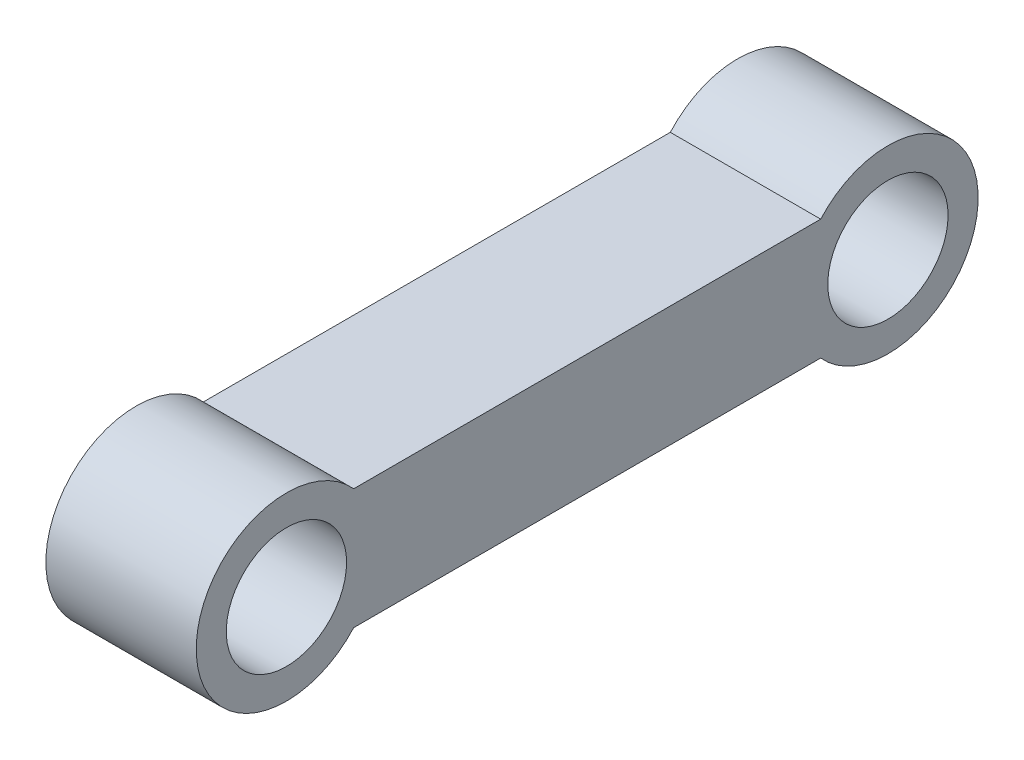
SolidWorks part; units mm, degrees
material "Thornel Mat VMA"
ref_plane "Front Plane" through (0, 0, 0) normal (0, 0, 1) x (1, 0, 0)
ref_plane "Top Plane" through (0, 0, 0) normal (0, 1, 0) x (1, 0, 0)
ref_plane "Right Plane" through (0, 0, 0) normal (1, 0, 0) x (0, 0, -1)
sketch "LinkFrame" plane through (0, 0, 0) normal (1, 0, 0) x (0, 0, -1)
  line L0 (-194.4922, 545.3519) -> (205.5078, 545.3519) construction
  line L1 (-149.7708, 585.3519) -> (160.7865, 585.3519)
  line L2 (-149.7708, 505.3519) -> (160.7865, 505.3519)
  arc A1 (160.7865, 505.3519) -> (160.7865, 585.3519) centre (205.5078, 545.3519) ccw
  arc A2 (-149.7708, 585.3519) -> (-149.7708, 505.3519) centre (-194.4922, 545.3519) ccw
  circle A5 centre (-194.4922, 545.3519) radius 40
  circle A6 centre (205.5078, 545.3519) radius 40
  dimension "D1" = 120
  dimension "D2" = 120
  dimension "D5" = 80
  dimension "D6" = 80
  dimension "D3" = 400
  dimension "D4" = 80
extrude "Boss-Extrude1" add sketch "LinkFrame" along normal blind 100
equation "\"D1@LinkFrame\" = 1.5 * \"HoleMountDiameter@PrintingPress.Assembly\""
equation "\"D2@LinkFrame\" = 1.5 * \"HoleMountDiameter@PrintingPress.Assembly\""
equation "\"LinkLength\" = 40cm"
equation "\"D3@LinkFrame\" = \"LinkLength\""
equation "\"D4@LinkFrame\" = \"HoleMountDiameter@PrintingPress.Assembly\""
equation "\"D5@LinkFrame\"=\"HoleMountDiameter@PrintingPress.Assembly\""
equation "\"D6@LinkFrame\"=\"HoleMountDiameter@PrintingPress.Assembly\""
equation "\"D1@Boss-Extrude1\"=\"RivetLength@PrintingPress.Assembly\""
